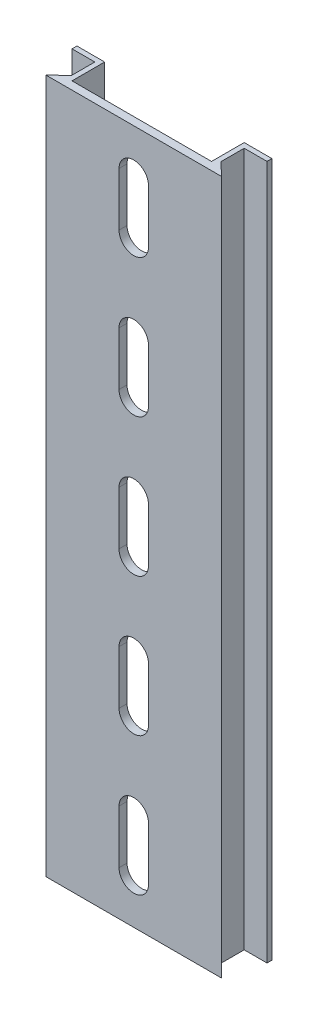
SolidWorks part; units mm, degrees
ref_plane "Front Plane" through (0, 0, 0) normal (0, 0, 1) x (1, 0, 0)
ref_plane "Top Plane" through (0, 0, 0) normal (0, 1, 0) x (1, 0, 0)
ref_plane "Right Plane" through (0, 0, 0) normal (1, 0, 0) x (0, 0, -1)
sketch "Sketch1" plane through (0, 0, 0) normal (0, 1, 0) x (1, 0, 0)
  line L0 (0, 0) -> (0, 1.4478)
  line L1 (-12.6365, 1.4478) -> (12.6365, 1.4478)
  line L2 (12.6365, 1.4478) -> (12.6365, 7.366)
  line L3 (12.6365, 7.366) -> (17.653, 7.366)
  line L4 (17.653, 7.366) -> (17.653, 6.477)
  line L5 (17.653, 6.477) -> (13.5255, 6.477)
  line L6 (13.5255, 6.477) -> (13.5255, 2.286)
  line L7 (13.5255, 2.286) -> (15.875, 0)
  line L8 (15.875, 0) -> (-15.875, 0)
  line L9 (-13.5255, 2.286) -> (-15.875, 0)
  line L10 (-13.5255, 6.477) -> (-13.5255, 2.286)
  line L11 (-17.653, 6.477) -> (-13.5255, 6.477)
  line L12 (-17.653, 7.366) -> (-17.653, 6.477)
  line L13 (-12.6365, 7.366) -> (-17.653, 7.366)
  line L14 (-12.6365, 1.4478) -> (-12.6365, 7.366)
  dimension "D1" = 15.875
  dimension "D2" = 13.5255
  dimension "D3" = 0.889
  dimension "D4" = 1.4478
  dimension "D5" = 7.366
  dimension "D6" = 0.889
  dimension "D7" = 2.286
  dimension "D8" = 17.653
extrude "Boss-Extrude1" add sketch "Sketch1" along normal mid plane 125.73 contours L1 L14 L13 L12 L11 L10 L9 L8 L0 | L8 L7 L6 L5 L4 L3 L2 L1 L0 region at (-7.9375, 0, -0.1913) region at (0.1913, 0, -0.7239)
sketch "Sketch2" plane through (0, 0, 0) normal (0, 0, 1) x (1, 0, 0)
  line L0 (0, -4.833) -> (0, 4.833) construction
  line L1 (-2.667, -4.833) -> (-2.667, 4.833)
  line L2 (2.667, -4.833) -> (2.667, 4.833)
  line L3 (-15.875, 0) -> (15.875, 0) construction
  line L4 (-15.875, 62.865) -> (-15.875, -62.865) construction
  line L5 (15.875, 62.865) -> (15.875, -62.865) construction
  arc A0 (-2.667, -4.833) -> (2.667, -4.833) centre (0, -4.833) ccw
  arc A1 (2.667, 4.833) -> (-2.667, 4.833) centre (0, 4.833) ccw
  point P3 (0, 0)
  point P15 (0, -7.5)
  point P16 (0, 7.5)
  dimension "D1" = 15
  dimension "D2" = 2.667
extrude "Cut-Extrude1" cut sketch "Sketch2" against normal through all
ref_plane "Plane1" through (0, 0, 0) normal (-1, 0, 0) x (0, 0, 1)
ref_plane "Plane2" through (0, 0, 0) normal (0, 1, 0) x (1, 0, 0)
pattern_linear "LPattern1" count 3 spacing 25 along (0, -1, 0) count 3 spacing 25 along (0, 1, 0) of "Cut-Extrude1"
